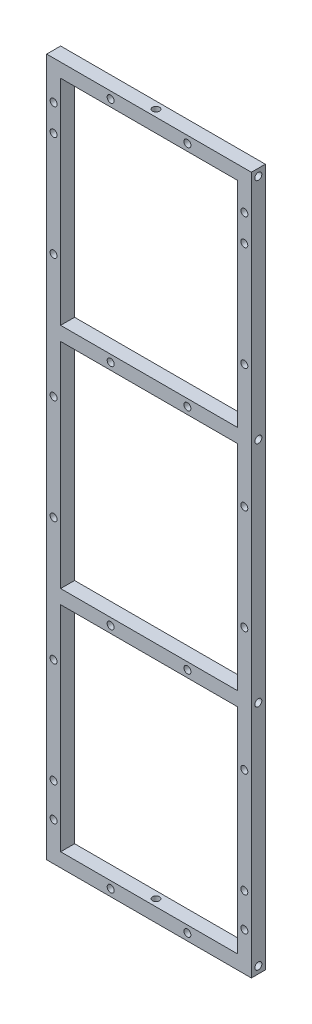
SolidWorks part; units mm, degrees
ref_plane "Front Plane" through (0, 0, 0) normal (0, 0, 1) x (1, 0, 0)
ref_plane "Top Plane" through (0, 0, 0) normal (0, 1, 0) x (1, 0, 0)
ref_plane "Right Plane" through (0, 0, 0) normal (1, 0, 0) x (0, 0, -1)
sketch "Sketch1" plane through (0, 0, 0) normal (0, 0, 1) x (1, 0, 0)
  line L0 (38, 144) -> (38, 52)
  line L9 (-44, -150) -> (44, -150)
  line L10 (-44, -150) -> (-44, 150)
  line L11 (-44, 150) -> (44, 150)
  line L12 (44, -150) -> (44, 150)
  line L15 (-38, -144) -> (38, -144)
  line L16 (-38, -144) -> (-38, -52)
  line L17 (-38, 144) -> (38, 144)
  line L21 (-38, 52) -> (38, 52)
  line L23 (-38, 46) -> (38, 46)
  line L25 (-38, -46) -> (38, -46)
  line L27 (-38, -52) -> (38, -52)
  line L33 (38, 46) -> (38, -46)
  line L34 (-38, 52) -> (-38, 144)
  line L35 (-38, -46) -> (-38, 46)
  line L36 (38, -52) -> (38, -144)
  point P0 (0, 0)
  point P4 (0, -46)
  point P6 (0, 0)
  point P20 (0, 0)
  point P21 (0, -150)
  dimension "D1" = 88
  dimension "D2" = 300
  dimension "D3" = 76
  dimension "D4" = 288
  dimension "D5" = 6
  dimension "D6" = 92
  dimension "D7" = 6
  dimension "D8" = 92
  dimension "D9" = 6
  dimension "D10" = 6
  dimension "D11" = 92
extrude "Boss-Extrude1" add sketch "Sketch1" along normal blind 6
sketch "Sketch2" plane through (44, 0, 0) normal (1, 0, 0) x (0, 0, -1)
  line L0 (-6, 150) -> (0, 150) construction
  circle A0 centre (-3, 147) radius 1.5
  circle A1 centre (-3, 49) radius 1.5
  circle A2 centre (-3, -49) radius 1.5
  circle A3 centre (-3, -147) radius 1.5
  dimension "D1" = 3
  dimension "D2" = 4
extrude "Cut-Extrude1" cut sketch "Sketch2" against normal blind 10
mirror "Mirror1" about plane through (0, 0, 0) normal (1, 0, 0) of "Cut-Extrude1"
sketch "Sketch3" plane through (0, 0, 6) normal (0, 0, 1) x (1, 0, 0)
  line L0 (-44, 150) -> (44, 150) construction
  line L1 (-44, -150) -> (-44, 150) construction
  circle A0 centre (-41, 133.5) radius 1.5
  circle A1 centre (41, 133.5) radius 1.5
  point P6 (0, 0)
  dimension "D1" = 16.5
  dimension "D2" = 3
extrude "Cut-Extrude2" cut sketch "Sketch3" against normal blind 10
sketch "Sketch4" plane through (0, 0, 6) normal (0, 0, 1) x (1, 0, 0)
  line L0 (-44, -150) -> (-44, 150) construction
  line L1 (44, -150) -> (44, 150) construction
  line L2 (-44, 150) -> (44, 150) construction
  circle A0 centre (-16.5, 147) radius 1.5
  circle A1 centre (16.5, 147) radius 1.5
  circle A2 centre (16.5, 49) radius 1.5
  circle A3 centre (-16.5, 49) radius 1.5
  circle A4 centre (16.5, -49) radius 1.5
  circle A5 centre (-16.5, -49) radius 1.5
  circle A6 centre (16.5, -147) radius 1.5
  circle A7 centre (-16.5, -147) radius 1.5
  circle A8 centre (-41.0409, 122) radius 1.5
  circle A9 centre (-41.0409, 77) radius 1.5
  circle A10 centre (40.9591, 122) radius 1.5
  circle A11 centre (40.9591, 77) radius 1.5
  circle A12 centre (40.9591, 24) radius 1.5
  circle A13 centre (40.9591, -21) radius 1.5
  circle A14 centre (40.9591, -74) radius 1.5
  circle A15 centre (40.9591, -119) radius 1.5
  circle A16 centre (-41.0409, 24) radius 1.5
  circle A17 centre (-41.0409, -21) radius 1.5
  circle A18 centre (-41.0409, -74) radius 1.5
  circle A19 centre (-41.0409, -119) radius 1.5
  dimension "D1" = 27.5
  dimension "D4" = 45
  dimension "D7" = 2
  dimension "D2" = 27.5
  dimension "D3" = 4
  dimension "D5" = 28
  dimension "D6" = 28
  dimension "D8" = 3
extrude "Cut-Extrude3" cut sketch "Sketch4" against normal blind 10
sketch "Sketch5" plane through (0, 150, 0) normal (0, 1, 0) x (1, 0, 0)
  line L0 (44, -6) -> (-44, -6) construction
  circle A0 centre (0, -3) radius 1.5
  point P5 (0, -6)
  dimension "D1" = 3
extrude "Cut-Extrude4" cut sketch "Sketch5" against normal blind 10
mirror "Mirror2" about plane through (0, 0, 0) normal (0, 1, 0) of "Cut-Extrude4"
ref_plane "Plane1" through (0, 0, 0) normal (0, 1, 0) x (1, 0, 0)
mirror "Mirror3" about plane through (0, 0, 0) normal (0, 1, 0) of "Cut-Extrude2"
